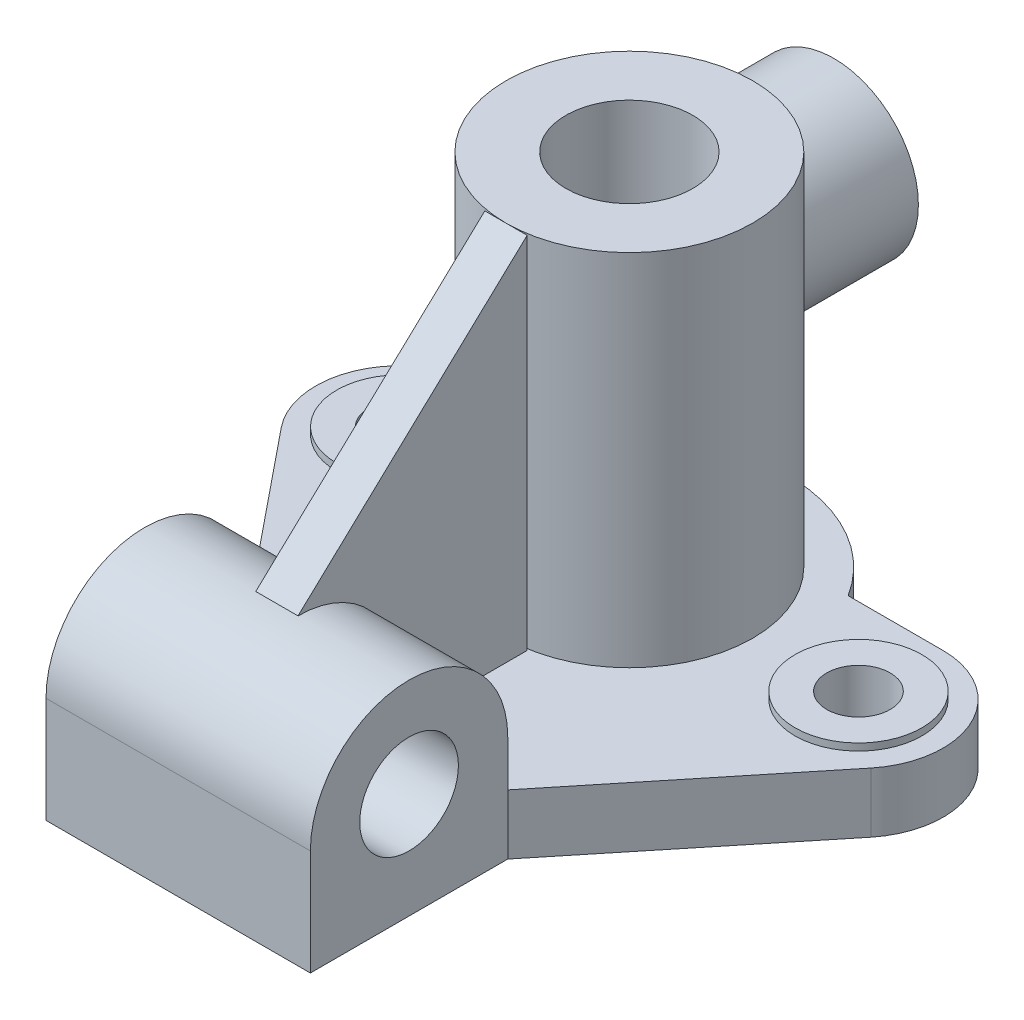
SolidWorks part; units mm, degrees
ref_plane "Front Plane" through (0, 0, 0) normal (0, 0, 1) x (1, 0, 0)
ref_plane "Top Plane" through (0, 0, 0) normal (0, 1, 0) x (1, 0, 0)
ref_plane "Right Plane" through (0, 0, 0) normal (1, 0, 0) x (0, 0, -1)
sketch "Sketch1" plane through (0, 0, 0) normal (0, 1, 0) x (1, 0, 0)
  line L0 (0, 87.651) -> (0, -141.1507) construction
  line L1 (-65, 24) -> (-38.0657, 24)
  line L2 (-37.5, -72) -> (37.5, -72)
  line L3 (-83.639, -15.1191) -> (-37.5, -72)
  line L4 (83.639, -15.1191) -> (37.5, -72)
  line L5 (65, 24) -> (38.0657, 24)
  circle A0 centre (0, 0) radius 35
  circle A1 centre (0, 0) radius 18
  circle A2 centre (-65, 0) radius 9
  circle A3 centre (-65, 0) radius 18
  circle A4 centre (65, 0) radius 18
  circle A5 centre (65, 0) radius 9
  arc A6 (-65, 24) -> (-83.639, -15.1191) centre (-65, 0) ccw
  arc A7 (38.0657, 24) -> (-38.0657, 24) centre (0, 0) ccw
  arc A8 (65, 24) -> (83.639, -15.1191) centre (65, 0) cw
  point P13 (0, 0)
  point P18 (0, -72)
  point P20 (0, 0)
  point P23 (0, 0)
  dimension "D1" = 36
  dimension "D2" = 70
  dimension "D3" = 18
  dimension "D4" = 36
  dimension "D6" = 48
  dimension "D7" = 90
  dimension "D5" = 65
  dimension "D8" = 75
  dimension "D9" = 72
extrude "Boss-Extrude1" add sketch "Sketch1" along normal blind 17 contours L0 A7 L1 A6 L3 L2 A0 A3 | A7 L0 A0 L2 L4 A8 L5 A4 | A1 L0 | L0 A1 region at (37.5869, 0, 24.0477) region at (-37.5869, 0, 24.0477) region at (7.6394, 0, 0) region at (-7.6394, 0, 0)
extrude "Boss-Extrude2" add sketch "Sketch1<4>" along normal blind 19 contours A3 A2 | A4 A5 region at (-82.4909, 0, 0) region at (47.5091, 0, 0)
sketch "Sketch1<4>" plane through (0, 0, 0) normal (0, 1, 0) x (1, 0, 0) same geometry as "Sketch1"
extrude "Boss-Extrude3" add sketch "Sketch1<6>" along normal blind 119 contours L0 A0 A1 | A0 L0 A1 region at (24.1953, 0, -24.1953) region at (-0.7826, 0, -26.5)
sketch "Sketch1<6>" plane through (0, 0, 0) normal (0, 1, 0) x (1, 0, 0) same geometry as "Sketch1"
sketch "Sketch4" plane through (0, 0, 0) normal (0, 0, 1) x (1, 0, 0)
  line L0 (-38.0657, 0) -> (38.0657, 0) construction
  circle A0 centre (0, 89) radius 12.5
  circle A1 centre (0, 89) radius 24
  dimension "D2" = 48
  dimension "D3" = 25
  dimension "D1" = 89
extrude "Boss-Extrude4" add sketch "Sketch4" against normal blind 40 from offset 18 offset against normal yes
sketch "Sketch5" plane through (0, 0, 0) normal (0, 1, 0) x (1, 0, 0)
  line L1 (-37.5, -72) -> (37.5, -72)
  line L2 (-37.5, -72) -> (-37.5, -128)
  line L3 (-37.5, -128) -> (37.5, -128)
  line L4 (37.5, -72) -> (37.5, -128)
  dimension "D1" = 75
  dimension "D2" = 56
extrude "Boss-Extrude5" add sketch "Sketch5" along normal blind 30
sketch "Sketch6" plane through (0, 0, 0) normal (1, 0, 0) x (0, 0, -1)
  line L0 (-100, 61.2838) -> (-100, -23.0796) construction
  line L1 (-128, 30) -> (-128, 0) construction
  line L2 (-128, 30) -> (-72, 30) construction
  line L3 (-128, 30) -> (-72, 30)
  circle A0 centre (-100, 30) radius 14
  arc A1 (-72, 30) -> (-128, 30) centre (-100, 30) ccw
  dimension "D2" = 28
  dimension "D1" = 28
extrude "Boss-Extrude6" add sketch "Sketch6" along normal mid plane 75 contours L3 A1 A0 region at (0, 44.6261, 100)
extrude "Cut-Extrude2" cut sketch "Sketch6<3>" against normal mid plane 75 contours L3 A0 | L3 A0 region at (0, 24.0582, 100) region at (0, 35.9418, 100)
sketch "Sketch6<3>" plane through (0, 0, 0) normal (1, 0, 0) x (0, 0, -1) same geometry as "Sketch6"
sketch "Sketch9" plane through (0, 0, 0) normal (1, 0, 0) x (0, 0, -1)
  line L0 (-35, 119) -> (-35, 17)
  line L1 (35, 119) -> (-35, 119) construction
  line L2 (-35, 119) -> (-100, 58)
  line L3 (-72, 30) -> (-72, 17)
  line L4 (35, 17) -> (-35, 17) construction
  line L5 (-35, 17) -> (-72, 17)
  arc A0 (-72, 30) -> (-128, 30) centre (-100, 30) ccw construction
  arc A1 (-72, 30) -> (-100, 58) centre (-100, 30) ccw
extrude "Boss-Extrude14" add sketch "Sketch9" along normal mid plane 12 separate body
